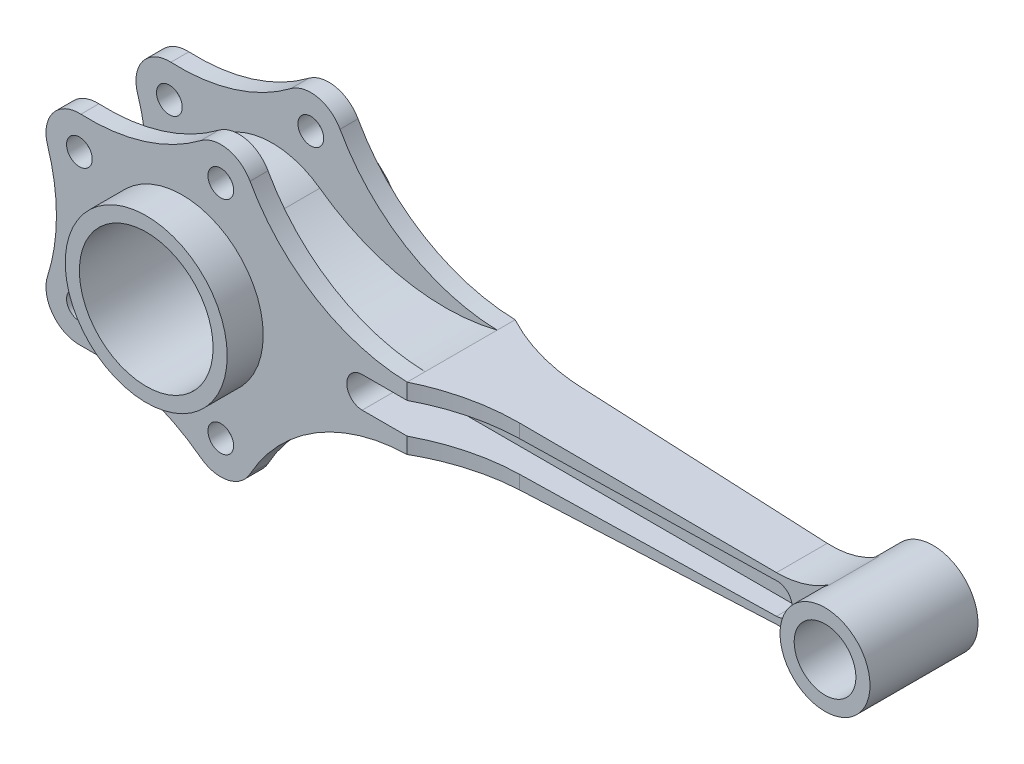
SolidWorks part; units mm, degrees
ref_plane "Front Plane" through (0, 0, 0) normal (0, 0, 1) x (1, 0, 0)
ref_plane "Top Plane" through (0, 0, 0) normal (0, 1, 0) x (1, 0, 0)
ref_plane "Right Plane" through (0, 0, 0) normal (1, 0, 0) x (0, 0, -1)
sketch "Sketch1" plane through (0, 0, 0) normal (0, 0, 1) x (1, 0, 0)
  line L0 (0, 0) -> (0, 28148.3336) construction
  line L1 (0, 0) -> (28148.3336, 0) construction
  line L2 (87.482, 12.19) -> (220, 8.7199)
  line L3 (87.482, -12.19) -> (220, -8.7199)
  line L4 (70, 0) -> (220, 0) construction
  line L5 (70, 6) -> (220, 6)
  line L6 (70, -6) -> (220, -6)
  circle A0 centre (0, 0) radius 31.5
  circle A1 centre (0, 0) radius 26
  circle A2 centre (15, 43) radius 5
  arc A3 (26.3737, 49.2959) -> (7.1819, 53.3864) centre (15, 43) ccw
  circle A4 centre (-40, 26) radius 5
  arc A5 (-39.4063, 38.9864) -> (-52.3769, 22.0235) centre (-40, 26) ccw
  circle A6 centre (250, 0) radius 17.5
  circle A7 centre (250, 0) radius 12
  arc A8 (220, 8.7199) -> (240.3054, 14.5693) centre (220.9162, 43.7079) ccw
  arc A9 (87.482, 12.19) -> (26.3737, 49.2959) centre (89.3668, 84.1653) cw
  arc A10 (7.1819, 53.3864) -> (-39.4063, 38.9864) centre (-36.118, 110.9113) cw
  circle A11 centre (-40, -26) radius 5
  arc A12 (-39.4063, -38.9864) -> (-52.3769, -22.0235) centre (-40, -26) cw
  circle A13 centre (15, -43) radius 5
  arc A14 (26.3737, -49.2959) -> (7.1819, -53.3864) centre (15, -43) cw
  arc A15 (7.1819, -53.3864) -> (-39.4063, -38.9864) centre (-36.118, -110.9113) ccw
  arc A16 (87.482, -12.19) -> (26.3737, -49.2959) centre (89.3668, -84.1653) ccw
  arc A17 (220, -8.7199) -> (240.3054, -14.5693) centre (220.9162, -43.7079) cw
  arc A18 (-52.3769, 22.0235) -> (-52.3769, -22.0235) centre (-120.9259, 0) cw
  arc A19 (70, 6) -> (70, -6) centre (70, 0) ccw
  arc A20 (220, -6) -> (220, 6) centre (220, 0) ccw
  point P28 (145, 0)
  dimension "D1" = 35
  dimension "D2" = 24
  dimension "D3" = 63
  dimension "D4" = 52
  dimension "D10" = 10
  dimension "D11" = 26
  dimension "D12" = 72
  dimension "D13" = 72
  dimension "D14" = 35
  dimension "D15" = 72
  dimension "D5" = 250
  dimension "D6" = 15
  dimension "D7" = 43
  dimension "D8" = 40
  dimension "D9" = 26
  dimension "D16" = 3
  dimension "D17" = 150
  dimension "D18" = 30
  dimension "D19" = 12
extrude "Boss-Extrude1" add sketch "Sketch1" along normal mid plane 70 contours A0 A1 region at (-30.609, 0, 0)
extrude "Boss-Extrude2" add sketch "Sketch1<3>" along normal mid plane 42 contours A5 A18 A12 A15 A14 A16 L3 A17 A6 A8 L2 A9 A3 A10 A20 L6 A19 L5 A13 A0 A2 A4 A11 region at (37.2826, 0, 0)
sketch "Sketch1<3>" plane through (0, 0, 0) normal (0, 0, 1) x (1, 0, 0) same geometry as "Sketch1"
extrude "Boss-Extrude3" add sketch "Sketch1<4>" along normal mid plane 5 contours L6 A20 L5 A19 region at (145, 0, 0)
sketch "Sketch1<4>" plane through (0, 0, 0) normal (0, 0, 1) x (1, 0, 0) same geometry as "Sketch1"
sketch "Sketch2" plane through (0, 0, 0) normal (0, 1, 0) x (1, 0, 0)
  line L0 (240.3054, -9.4227) -> (122.1887, -12)
  line L1 (26.3737, -21) -> (87.482, -21) construction
  line L2 (87.482, -21) -> (220, -21) construction
  line L3 (240.3054, -21) -> (240.3054, 21) construction
  line L4 (87.482, -21) -> (240.3054, -21)
  line L5 (240.3054, -21) -> (240.3054, -9.4227)
  line L6 (0, 0) -> (50000, 0) construction
  line L7 (240.3054, 9.4227) -> (122.1887, 12)
  line L8 (240.3054, 21) -> (240.3054, 9.4227)
  line L9 (87.482, 21) -> (240.3054, 21)
  line L10 (87.482, -21) -> (87.482, 21) construction
  arc A0 (122.1887, -12) -> (87.482, -21) centre (123.8903, -89.9814) ccw
  arc A1 (122.1887, 12) -> (87.482, 21) centre (123.8903, 89.9814) cw
  dimension "D2" = 78
  dimension "D1" = 2.5
  dimension "D3" = 24
extrude "Cut-Extrude1" cut sketch "Sketch2" against normal through all both and the other way through all
extrude "Boss-Extrude4" add sketch "Sketch1<5>" along normal mid plane 42 contours A6 A7 region at (258.0305, 14.9894, 0)
sketch "Sketch1<5>" plane through (0, 0, 0) normal (0, 0, 1) x (1, 0, 0) same geometry as "Sketch1"
sketch "Sketch3" plane through (0, 0, 0) normal (0, 0, 1) x (1, 0, 0)
  line L0 (0, 0) -> (50000, 0) construction
  arc A0 (87.482, 12.19) -> (18.4964, 25.4977) centre (67.233, 92.6821) cw
  circle A1 centre (0, 0) radius 31.5 construction
  circle A2 centre (0, 0) radius 31.5 construction
  arc A3 (87.482, -12.19) -> (18.4964, -25.4977) centre (67.233, -92.6821) ccw
  arc A4 (26.3737, 49.2959) -> (7.1819, 53.3864) centre (15, 43) ccw construction
  arc A5 (-39.4063, 38.9864) -> (7.1819, 53.3864) centre (-36.118, 110.9113) ccw construction
  arc A6 (-39.4063, 38.9864) -> (-52.3769, 22.0235) centre (-40, 26) ccw construction
  arc A7 (-52.3769, -22.0235) -> (-52.3769, 22.0235) centre (-120.9259, 0) ccw construction
  arc A8 (-52.3769, -22.0235) -> (-39.4063, -38.9864) centre (-40, -26) ccw construction
  arc A9 (7.1819, -53.3864) -> (-39.4063, -38.9864) centre (-36.118, -110.9113) ccw construction
  arc A10 (7.1819, -53.3864) -> (26.3737, -49.2959) centre (15, -43) ccw construction
  arc A11 (87.482, -12.19) -> (26.3737, -49.2959) centre (89.3668, -84.1653) ccw construction
  arc A12 (26.3737, 49.2959) -> (7.1819, 53.3864) centre (15, 43) ccw
  arc A13 (-39.4063, 38.9864) -> (7.1819, 53.3864) centre (-36.118, 110.9113) ccw
  arc A14 (-39.4063, 38.9864) -> (-52.3769, 22.0235) centre (-40, 26) ccw
  arc A15 (-52.3769, -22.0235) -> (-52.3769, 22.0235) centre (-120.9259, 0) ccw
  arc A16 (-52.3769, -22.0235) -> (-39.4063, -38.9864) centre (-40, -26) ccw
  arc A17 (7.1819, -53.3864) -> (-39.4063, -38.9864) centre (-36.118, -110.9113) ccw
  arc A18 (7.1819, -53.3864) -> (26.3737, -49.2959) centre (15, -43) ccw
  arc A19 (87.482, -12.19) -> (26.3737, -49.2959) centre (89.3668, -84.1653) ccw
  arc A20 (26.3737, 49.2959) -> (87.482, 12.19) centre (89.3668, 84.1653) ccw construction
  arc A21 (26.3737, 49.2959) -> (87.482, 12.19) centre (89.3668, 84.1653) ccw
  arc A22 (18.4964, 25.4977) -> (31.5, 0) centre (0, 0) ccw
  dimension "D1" = 83
extrude "Cut-Extrude2" cut sketch "Sketch3" against normal mid plane 28 contours L0 A15 A16 A17 A18 A19 A3 A22 | A15 L0 A22 A0 A21 A12 A13 A14 region at (51.852, 12.9487, 0)
